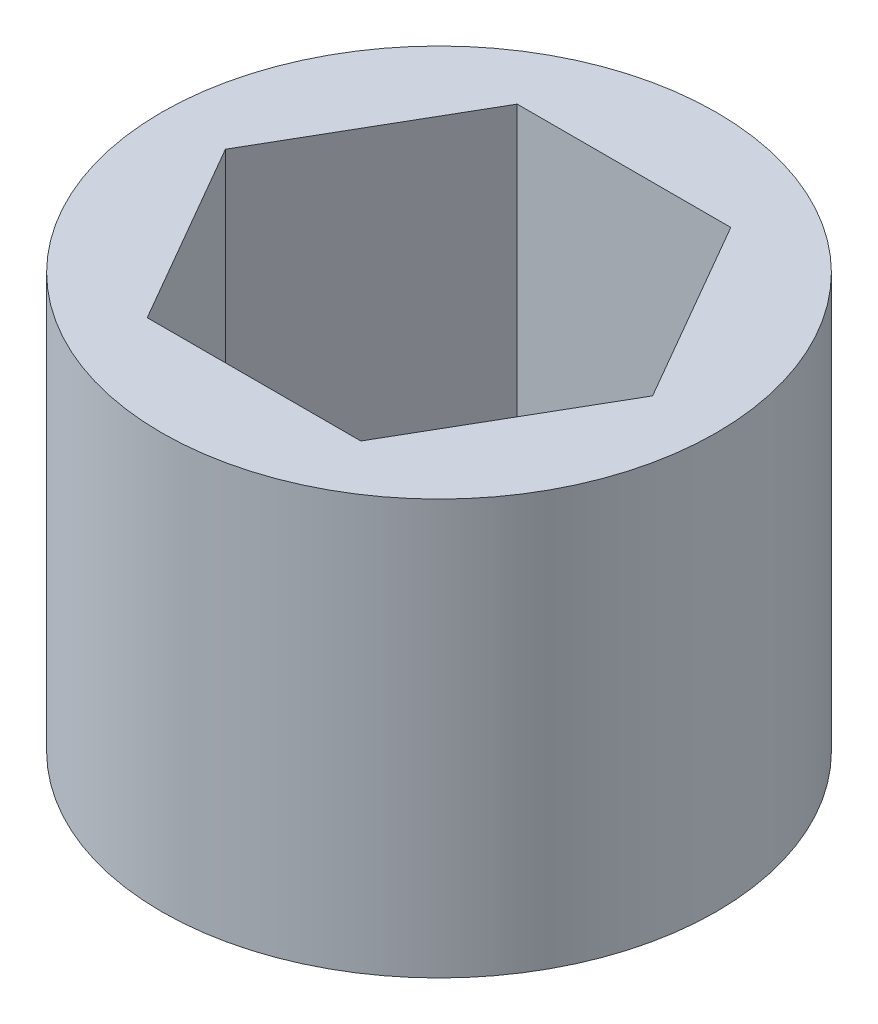
SolidWorks part; units mm, degrees
material "PET"
ref_plane "Front Plane" through (0, 0, 0) normal (0, 0, 1) x (1, 0, 0)
ref_plane "Top Plane" through (0, 0, 0) normal (0, 1, 0) x (1, 0, 0)
ref_plane "Right Plane" through (0, 0, 0) normal (1, 0, 0) x (0, 0, -1)
sketch "Sketch1" plane through (0, 0, 0) normal (0, 1, 0) x (1, 0, 0)
  line L1 (7.3323, 0) -> (3.6662, 6.35)
  line L2 (3.6662, 6.35) -> (-3.6662, 6.35)
  line L3 (-3.6662, 6.35) -> (-7.3323, 0)
  line L4 (-7.3323, 0) -> (-3.6662, -6.35)
  line L5 (-3.6662, -6.35) -> (3.6662, -6.35)
  line L6 (3.6662, -6.35) -> (7.3323, 0)
  circle A0 centre (0, 0) radius 6.35 construction
  circle A1 centre (0, 0) radius 9.525
  dimension "D1" = 19.05
  dimension "D2" = 12.7
extrude "Boss-Extrude1" add sketch "Sketch1" along normal blind 14.2367
